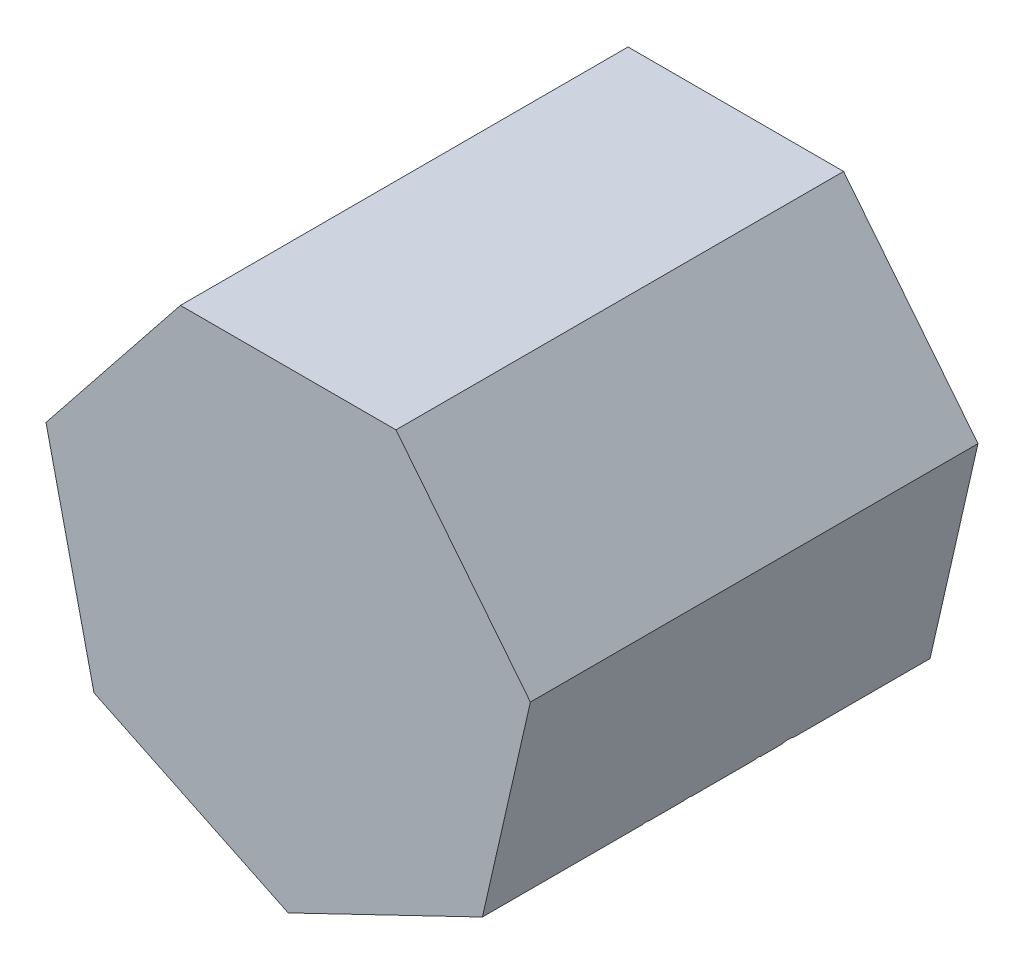
SolidWorks part; units mm, degrees
ref_plane "Front Plane" through (0, 0, 0) normal (0, 0, 1) x (1, 0, 0)
ref_plane "Top Plane" through (0, 0, 0) normal (0, 1, 0) x (1, 0, 0)
ref_plane "Right Plane" through (0, 0, 0) normal (1, 0, 0) x (0, 0, -1)
sketch "Sketch1" plane through (0, 0, 0) normal (0, 0, 1) x (1, 0, 0)
  line L1 (0, -110.9916) -> (86.7767, -69.2021)
  line L2 (86.7767, -69.2021) -> (108.2088, 24.698)
  line L3 (108.2088, 24.698) -> (48.1575, 100)
  line L4 (48.1575, 100) -> (-48.1575, 100)
  line L5 (-48.1575, 100) -> (-108.2088, 24.698)
  line L6 (-108.2088, 24.698) -> (-86.7767, -69.2021)
  line L7 (-86.7767, -69.2021) -> (0, -110.9916)
  circle A0 centre (0, 0) radius 100 construction
  dimension "D1" = 200
extrude "Boss-Extrude1" add sketch "Sketch1" along normal blind 200
sketch "Sketch2" plane through (-78.1831, 62.349, 0) normal (-0.7818, 0.6235, 0) x (0, 0, 1)
  text T0 "Andres" font "Century Gothic" height 20
extrude "Cut-Extrude1" cut sketch "Sketch2" against normal blind 1
sketch "Sketch4" plane through (-97.4928, -22.2521, 0) normal (-0.9749, -0.2225, 0) x (0, 0, 1)
  text T0 "Billy" font "Century Gothic" height 20
extrude "Cut-Extrude3" cut sketch "Sketch4" against normal blind 1
sketch "Sketch7" plane through (-43.3884, -90.0969, 0) normal (-0.4339, -0.901, 0) x (-0.901, 0.4339, 0)
  text T0 "ALEX" font "Century Gothic" height in points 72
extrude "Cut-Extrude5" cut sketch "Sketch7" against normal blind 2
sketch "Sketch8" plane through (43.3884, -90.0969, 0) normal (0.4339, -0.901, 0) x (0.901, 0.4339, 0)
  text T0 "Cameron" font "Century Gothic" height 14
extrude "Cut-Extrude6" cut sketch "Sketch8" against normal blind 1
